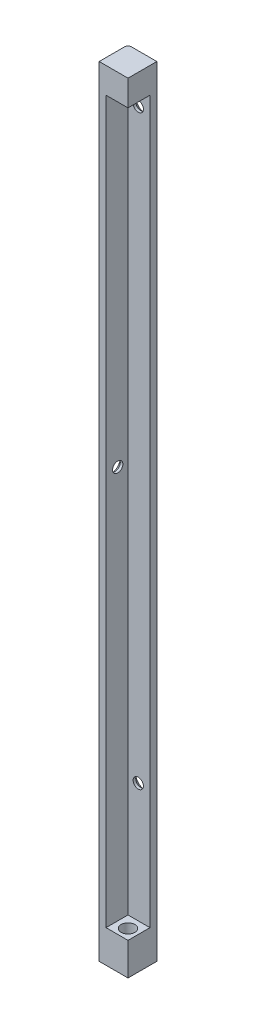
SolidWorks part; units mm, degrees
material "Aluminum"
ref_plane "Front Plane" through (0, 0, 0) normal (0, 0, 1) x (1, 0, 0)
ref_plane "Top Plane" through (0, 0, 0) normal (0, 1, 0) x (1, 0, 0)
ref_plane "Right Plane" through (0, 0, 0) normal (1, 0, 0) x (0, 0, -1)
sketch "Sketch1" plane through (0, 0, 0) normal (0, 1, 0) x (1, 0, 0)
  line L0 (0, 0) -> (0, 9)
  line L1 (0, 9) -> (9, 9)
  line L2 (2, 0) -> (2, 7)
  line L3 (2, 7) -> (9, 7)
  line L4 (9, 9) -> (9, 7)
  line L5 (0, 0) -> (2, 0)
  dimension "D1" = 9
  dimension "D2" = 9
  dimension "D3" = 2
extrude "Boss-Extrude1" add sketch "Sketch1" along normal blind 221.5
hole_wizard "CSK for M3 Countersunk Flat Head Screw1" positions "Sketch5" profile "Sketch4" countersink size "M3" standard "ISO" end condition through all
sketch "Sketch5" plane through (0, 0, 0) normal (-1, 0, 0) x (0, 0, 1)
  line L6 (-9, 221.5) -> (-9, 0) construction
  line L8 (-9, 110.75) -> (50.482, 110.75) construction
  point P16 (-4, 120)
  dimension "D1" = 9.25
  dimension "D6" = 5
sketch "Sketch4" plane through (0, 120, -4) normal (0, 1, 0) x (0, 0, 1)
  line L0 (0, 0) -> (0, 9)
  line L1 (0, 9) -> (1.5, 9)
  line L2 (1.5, 9) -> (1.5, 1.25)
  line L3 (1.5, 1.25) -> (2.75, 0)
  line L5 (2.75, 0) -> (0, 0)
  line L6 (-1.5, 1.25) -> (-2.75, 0) construction
  line L11 (0, -6.35) -> (0, 107.95) construction
  dimension "Thru Hole Dia." = 3
  dimension "Thru Hole Depth" = 9
  dimension "Near C'Sink Dia." = 5.5
  dimension "Near C'Sink Angle" = 90
hole_wizard "CSK for M3 Countersunk Flat Head Screw4" positions "Sketch11" profile "Sketch10" countersink size "M3" standard "ISO" end condition through all
sketch "Sketch11" plane through (0, 0, -9) normal (0, 0, -1) x (-1, 0, 0)
  line L4 (0, 221.5) -> (0, 0) construction
  line L7 (0, 110.75) -> (77.647, 110.75) construction
  point P4 (-5, 40.25)
  point P33 (-5, 211)
  dimension "D8" = 5
sketch "Sketch10" plane through (5, 40.25, -9) normal (1, 0, 0) x (0, 1, 0)
  line L0 (0, 0) -> (0, 9)
  line L1 (0, 9) -> (1.5, 9)
  line L2 (1.5, 9) -> (1.5, 1.25)
  line L3 (1.5, 1.25) -> (2.75, 0)
  line L5 (2.75, 0) -> (0, 0)
  line L6 (-1.5, 1.25) -> (-2.75, 0) construction
  line L11 (0, -6.35) -> (0, 107.95) construction
  dimension "Thru Hole Dia." = 3
  dimension "Thru Hole Depth" = 9
  dimension "Near C'Sink Dia." = 5.5
  dimension "Near C'Sink Angle" = 90
sketch "Sketch12" plane through (0, 0, 0) normal (0, -1, 0) x (1, 0, 0)
  line L0 (2, -7) -> (9, -7) construction
  line L1 (1, -7) -> (9, -7)
  line L2 (1, -7) -> (1, 0)
  line L3 (1, 0) -> (9, 0)
  line L4 (9, -7) -> (9, 0)
  line L5 (9, -7) -> (9, -9) construction
extrude "Boss-Extrude2" add sketch "Sketch12" against normal blind 5.5
sketch "Sketch13" plane through (0, 221.5, 0) normal (0, 1, 0) x (1, 0, 0)
  line L0 (0, 8) -> (1, 9)
  line L1 (0, 9) -> (0, 0) construction
  line L2 (9, 9) -> (0, 9) construction
  line L3 (0, 8) -> (0, 9)
  line L4 (0, 9) -> (1, 9)
  dimension "D1" = 1
  dimension "D2" = 1
extrude "Cut-Extrude1" cut sketch "Sketch13" against normal blind 359
sketch "Sketch14" plane through (0, 0, 0) normal (0, -1, 0) x (1, 0, 0)
  line L0 (0, 0) -> (9, 0)
  line L1 (9, 0) -> (9, -9)
  line L2 (9, -9) -> (1, -9)
  line L3 (1, -9) -> (0, -8)
  line L4 (0, -8) -> (0, 0)
extrude "Boss-Extrude3" add sketch "Sketch14" along normal blind 3
sketch "Sketch18" plane through (0, 221.5, 0) normal (0, 1, 0) x (1, 0, 0)
  line L1 (0, 0) -> (9, 0)
  line L2 (0, 0) -> (0, 8)
  line L3 (1, 9) -> (9, 9)
  line L4 (9, 0) -> (9, 9)
  line L5 (1, 9) -> (0, 8)
  dimension "D1" = 9
  dimension "D2" = 9
extrude "Boss-Extrude4" add sketch "Sketch18" along normal blind 2.5 and the other way blind 6
sketch "Sketch19" plane through (0, 0, 0) normal (-1, 0, 0) x (0, 0, 1)
  line L1 (0, 224) -> (-0.6, 224)
  line L2 (0, 224) -> (0, -3)
  line L3 (0, -3) -> (-0.6, -3)
  line L4 (-0.6, 224) -> (-0.6, -3)
  line L5 (0, 224) -> (0, -3) construction
  dimension "D1" = 0.6
extrude "Cut-Extrude2" cut sketch "Sketch19" against normal blind 10
sketch "Sketch20" plane through (0, 0, 0) normal (-1, 0, 0) x (0, 0, 1)
  line L1 (-0.6, 224) -> (-16.2047, 224)
  line L2 (-0.6, 224) -> (-0.6, 222)
  line L3 (-0.6, 222) -> (-16.2047, 222)
  line L4 (-16.2047, 224) -> (-16.2047, 222)
  dimension "D1" = 2
extrude "Cut-Extrude3" cut sketch "Sketch20" against normal blind 10
sketch "Sketch21" plane through (0, 0, -9) normal (0, 0, -1) x (-1, 0, 0)
  line L0 (-1, -3) -> (-9, -3) construction
  line L1 (-9, 222) -> (-8.4, 222)
  line L2 (-9, 222) -> (-9, -3)
  line L3 (-9, -3) -> (-8.4, -3)
  line L4 (-8.4, 222) -> (-8.4, -3)
  dimension "D1" = 0.6
extrude "Cut-Extrude4" cut sketch "Sketch21" against normal blind 10
sketch "Sketch22" plane through (0, 0, -9) normal (0, 0, -1) x (-1, 0, 0)
  line L0 (0, -3) -> (0, 222) construction
  line L1 (-8.4, -3) -> (0, -3)
  line L2 (-8.4, -3) -> (-8.4, 2.5)
  line L3 (-8.4, 2.5) -> (0, 2.5)
  line L4 (0, -3) -> (0, 2.5)
  dimension "D1" = 5.5
extrude "Cut-Extrude5" cut sketch "Sketch22" against normal blind 10
sketch "Sketch26" plane through (0, 2.5, 0) normal (0, -1, 0) x (1, 0, 0)
  line L0 (8.4, -9) -> (8.4, -0.6)
  line L1 (8.4, -0.6) -> (0, -0.6)
  line L2 (0, -0.6) -> (0, -8)
  line L3 (0, -8) -> (1, -9)
  line L4 (1, -9) -> (8.4, -9)
extrude "Boss-Extrude5" add sketch "Sketch26" along normal blind 2
hole_wizard "Tap Drill for M4x0.7 Tap1" positions "Sketch28" profile "Sketch27" hole size "M4x0.7" standard "ANSI Metric" end condition up to next
sketch "Sketch28" plane through (0, 0.5, 0) normal (0, -1, 0) x (-1, 0, 0)
  point P0 (-5.4, 3.6)
sketch "Sketch27" plane through (5.4, 0.5, -3.6) normal (1, 0, 0) x (0, 0, -1)
  line L0 (0, 0) -> (0, 5)
  line L1 (0, 5) -> (2, 5)
  line L2 (2, 5) -> (2, 0)
  line L5 (2, 0) -> (0, 0)
  line L11 (0, -6.35) -> (0, 107.95) construction
  dimension "Thru Hole Dia." = 4
  dimension "Thru Hole Depth" = 5
sketch "Sketch29" plane through (0, 222, 0) normal (0, 1, 0) x (1, 0, 0)
  line L0 (0, 8) -> (1, 9)
  line L1 (1, 9) -> (0, 9)
  line L2 (0, 9) -> (0, 8)
extrude "Boss-Extrude6" add sketch "Sketch29" against normal blind 221.5
fillet "Fillet1" radius 1 1 edges at (0, 111.25, -9)
sketch "Sketch30" plane through (0, 0.5, 0) normal (0, -1, 0) x (1, 0, 0)
  line L0 (0, -0.6) -> (8.4, -0.6)
  line L1 (8.4, -0.6) -> (8.4, -9)
  line L2 (8.4, -9) -> (1, -9)
  line L3 (0, -0.6) -> (0, -8)
  arc A0 (0, -8) -> (1, -9) centre (1, -8) ccw
  circle A1 centre (5.4, -3.6) radius 2
extrude "Boss-Extrude7" add sketch "Sketch30" along normal blind 4.5
ref_plane "Plane1" through (0, 222, -8) normal (0, 0, 1) x (1, 0, 0)
sketch "Sketch32" plane through (0, 222, 0) normal (0, 1, 0) x (1, 0, 0)
  line L0 (0, 0.6) -> (8.4, 0.6)
  line L1 (8.4, 0.6) -> (8.4, 9)
  line L2 (8.4, 9) -> (1, 9)
  line L3 (0, 8) -> (0, 0.6)
  arc A0 (0, 8) -> (1, 9) centre (1, 8) cw
extrude "Boss-Extrude8" add sketch "Sketch32" along normal blind 1
